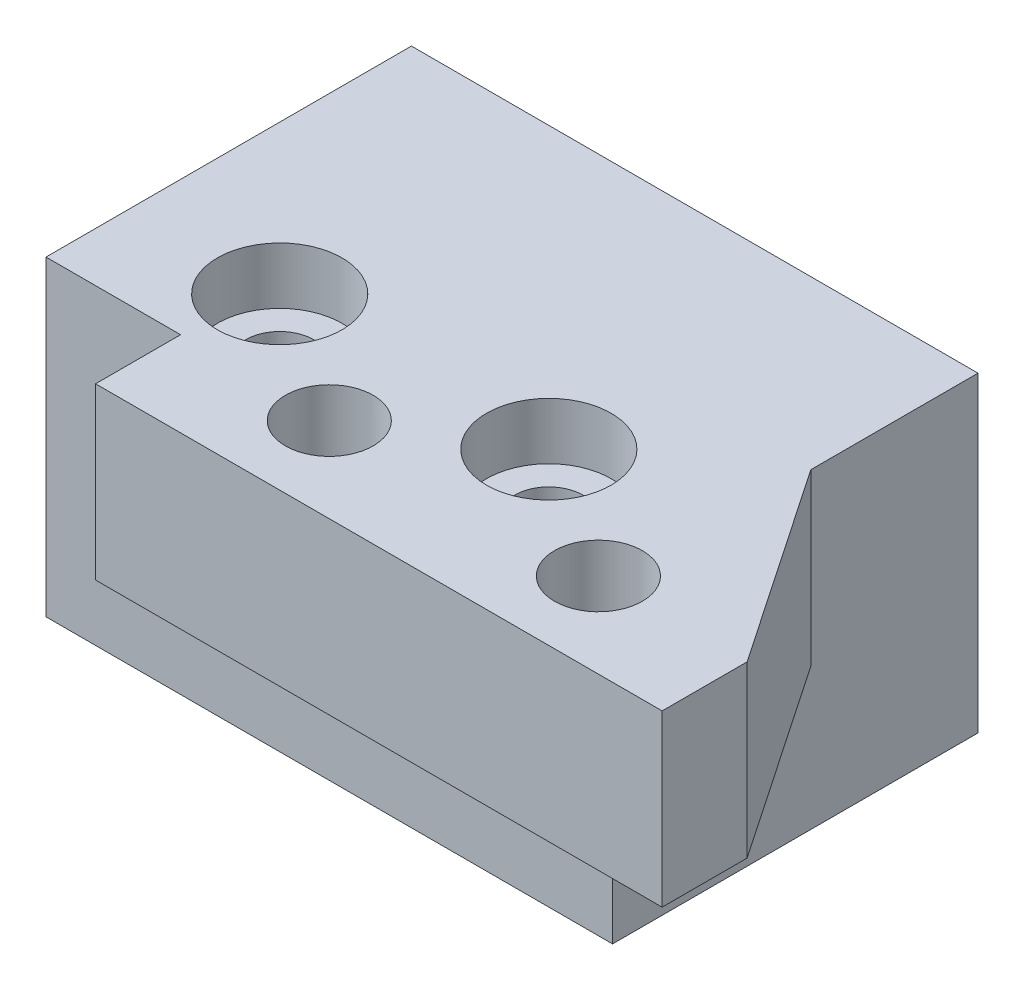
SolidWorks part; units mm, degrees
ref_plane "Front Plane" through (0, 0, 0) normal (0, 0, 1) x (1, 0, 0)
ref_plane "Top Plane" through (0, 0, 0) normal (0, 1, 0) x (1, 0, 0)
ref_plane "Right Plane" through (0, 0, 0) normal (1, 0, 0) x (0, 0, -1)
sketch "Sketch1" plane through (0, 0, 0) normal (0, 1, 0) x (1, 0, 0)
  line L0 (5.25, 3) -> (14.75, 3) construction
  line L1 (0, 0) -> (20, 0)
  line L2 (0, 0) -> (0, 12.9)
  line L3 (0, 12.9) -> (20, 12.9)
  line L4 (20, 0) -> (20, 12.9)
  circle A0 centre (5.25, 3) radius 1.175
  circle A1 centre (14.75, 3) radius 1.175
  point P9 (10, 3)
  point P10 (10, 0)
  dimension "D3" = 9.5
  dimension "D4" = 3
  dimension "D5" = 2.35
  dimension "D6" = 2.35
  dimension "D1" = 12.9
  dimension "D2" = 20
extrude "Boss-Extrude1" add sketch "Sketch1" along normal blind 11
sketch "Sketch2" plane through (0, 0, 0) normal (0, 0, 1) x (1, 0, 0)
  line L1 (4.75, 11) -> (24.75, 11)
  line L2 (4.75, 11) -> (4.75, 5)
  line L3 (4.75, 5) -> (24.75, 5)
  line L4 (24.75, 11) -> (24.75, 5)
  line L5 (0, 11) -> (20, 11) construction
  line L6 (0, 11) -> (0, 0) construction
  dimension "D1" = 6
  dimension "D2" = 20
  dimension "D3" = 4.75
extrude "Boss-Extrude2" add sketch "Sketch2" along normal blind 3
sketch "Sketch3" plane through (0, 11, 0) normal (0, 1, 0) x (1, 0, 0)
  point P0 (5.25, 3)
  point P1 (14.75, 3)
hole_wizard "CBORE for M2 SHCS1" positions "Sketch3" profile "Sketch4" counterbore size "M2" standard "ANSI Metric" end condition through all
sketch "Sketch4" plane through (5.25, 11, -3) normal (1, 0, 0) x (0, 0, 1)
  line L0 (0, 0) -> (0, 11)
  line L1 (0, 11) -> (1.2, 11)
  line L3 (1.2, 11) -> (1.2, 2)
  line L4 (1.2, 2) -> (2.2, 2)
  line L5 (2.2, 2) -> (2.2, 0)
  line L7 (2.2, 0) -> (0, 0)
  line L11 (0, -6.35) -> (0, 107.95) construction
  dimension "Thru Hole Dia." = 2.4
  dimension "Thru Hole Depth" = 11
  dimension "C'Bore Dia." = 4.4
  dimension "C'Bore Depth" = 2
chamfer "Chamfer1" distance 4.75 distance2 7 1 edges at (20, 8, 0) first distance on face at (22.375, 8, 0)
sketch "Sketch5" plane through (0, 11, 0) normal (0, 1, 0) x (1, 0, 0)
  line L0 (24.75, -3) -> (4.75, -3) construction
  line L1 (10, 0) -> (19.5, 0) construction
  circle A0 centre (10, 0) radius 1.55
  circle A1 centre (19.5, 0) radius 1.55
  point P6 (14.75, -3)
  point P7 (14.75, 0)
  dimension "D1" = 3.1
  dimension "D2" = 3.1
  dimension "D3" = 9.5
  dimension "D4" = 3
extrude "Cut-Extrude1" cut sketch "Sketch5" against normal blind 6
